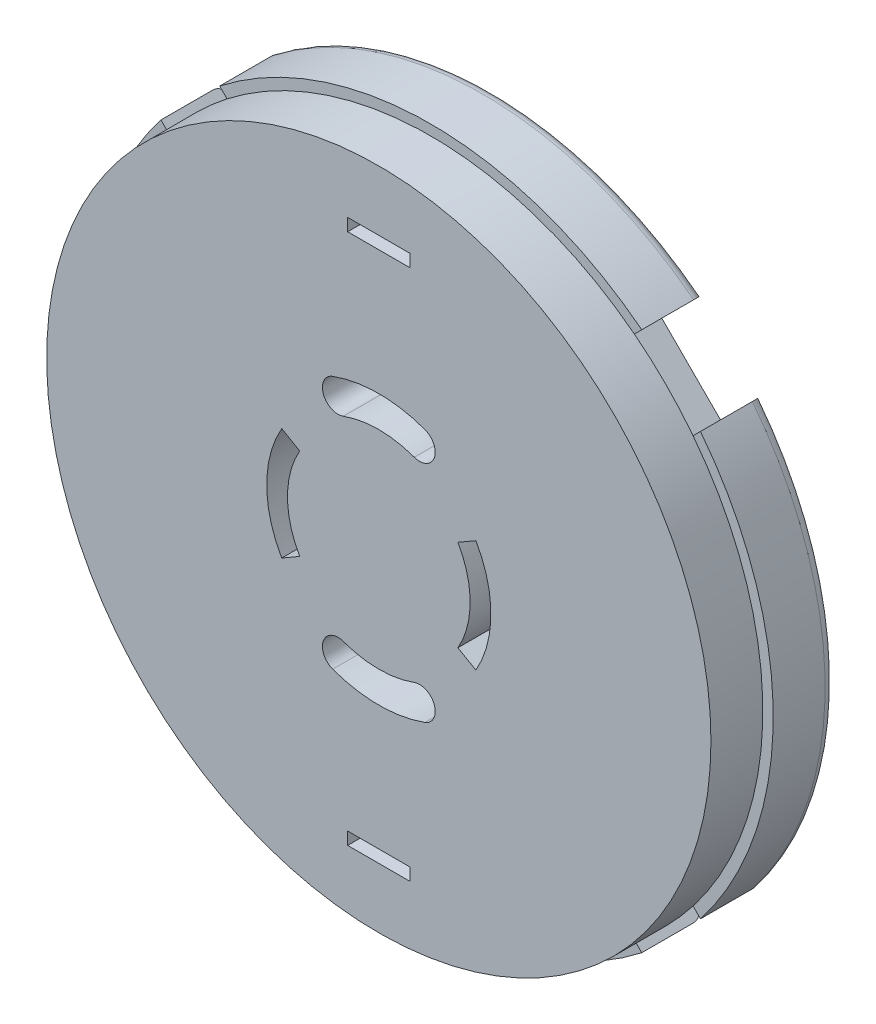
SolidWorks part; units mm, degrees
material "ABS"
ref_plane "Front Plane" through (0, 0, 0) normal (0, 0, 1) x (1, 0, 0)
ref_plane "Top Plane" through (0, 0, 0) normal (0, 1, 0) x (1, 0, 0)
ref_plane "Right Plane" through (0, 0, 0) normal (1, 0, 0) x (0, 0, -1)
sketch "Sketch1" plane through (0, 0, 0) normal (0, 0, 1) x (1, 0, 0)
  circle A0 centre (0, 0) radius 16.5
  dimension "D1" = 33
extrude "Boss-Extrude1" add sketch "Sketch1" against normal blind 3
sketch "Sketch2" plane through (0, 0, -3) normal (0, 0, -1) x (-1, 0, 0)
  circle A0 centre (0, 0) radius 4.5
  dimension "D1" = 9
extrude "Boss-Extrude2" add sketch "Sketch2" along normal blind 2
sketch "Sketch3" plane through (0, 0, -3) normal (0, 0, -1) x (-1, 0, 0)
  line L0 (10.253, 13.0815) -> (8.1317, 10.9602)
  line L5 (8.1317, 10.9602) -> (10.9602, 8.1317)
  line L6 (10.9602, 8.1317) -> (13.0815, 10.253)
  line L7 (13.0815, 10.253) -> (10.253, 13.0815)
  line L8 (0, 0) -> (9.5459, 9.5459) construction
  line L9 (0, 0) -> (0, 16.5) construction
  circle A0 centre (0, 0) radius 16.5 construction
  dimension "D2" = 4
  dimension "D1" = 45
  dimension "D3" = 3
extrude "Cut-Extrude1" cut sketch "Sketch3" against normal through all
pattern_circular "CirPattern1" count 4 over 360 about axis through (0, 0, -3) along (0, 0, 1) of "Cut-Extrude1" reverse direction yes
sketch "Sketch4" plane through (0, 0, 0) normal (0, 0, 1) x (1, 0, 0)
  circle A0 centre (0, 0) radius 16
  dimension "D1" = 32
extrude "Boss-Extrude3" add sketch "Sketch4" along normal blind 2.5
sketch "Sketch6" plane through (0, 0, -3) normal (0, 0, -1) x (-1, 0, 0)
  line L0 (-4.6765, 2.7) -> (-3.8105, 2.2)
  line L1 (-4.6765, -2.7) -> (-3.8105, -2.2)
  line L2 (0, 0) -> (-4.4, 0) construction
  line L3 (-4.6765, 2.7) -> (-4.6765, -2.7) construction
  arc A0 (-4.6765, 2.7) -> (-4.6765, -2.7) centre (0, 0) ccw
  arc A1 (-3.8105, 2.2) -> (-3.8105, -2.2) centre (0, 0) ccw
  dimension "D1" = 1
  dimension "D2" = 4.4
  dimension "D3" = 60
  dimension "D4" = 5.4
extrude "Cut-Extrude2" cut sketch "Sketch6" against normal through all
pattern_circular "CirPattern2" count 2 over 360 about axis through (0, 0, -3) along (0, 0, 1) of "Cut-Extrude2" reverse direction yes
sketch "Sketch7" plane through (0, 0, -3) normal (0, 0, -1) x (-1, 0, 0)
  line L0 (0, 0) -> (0, 5.75) construction
  line L1 (0, 0) -> (-1.9666, 5.4032) construction
  line L2 (0, 0) -> (1.9666, 5.4032) construction
  line L3 (-1.9666, 5.4032) -> (1.9666, 5.4032) construction
  arc A0 (-1.9666, 5.4032) -> (1.9666, 5.4032) centre (0, 0) cw construction
  arc A1 (2.2231, 6.108) -> (-2.2231, 6.108) centre (0, 0) ccw
  arc A2 (1.7101, 4.6985) -> (-1.7101, 4.6985) centre (0, 0) ccw
  arc A3 (1.7101, 4.6985) -> (2.2231, 6.108) centre (1.9666, 5.4032) ccw
  arc A4 (-2.2231, 6.108) -> (-1.7101, 4.6985) centre (-1.9666, 5.4032) ccw
  point P4 (0, 5.75)
  dimension "D1" = 0.75
  dimension "D2" = 5
  dimension "D3" = 40
  dimension "D4" = 3.9332
extrude "Cut-Extrude3" cut sketch "Sketch7" against normal through all
pattern_circular "CirPattern3" count 2 over 360 about axis through (0, 0, -3) along (0, 0, 1) of "Cut-Extrude3" reverse direction yes
sketch "Sketch8" plane through (0, 0, -3) normal (0, 0, -1) x (-1, 0, 0)
  line L0 (8.4853, -3.5355) -> (3.5355, -8.4853)
  line L1 (3.5355, -8.4853) -> (5.6569, -10.6066)
  line L2 (5.6569, -10.6066) -> (10.6066, -5.6569)
  line L3 (10.6066, -5.6569) -> (8.4853, -3.5355)
  line L4 (0, 0) -> (6.0104, -6.0104) construction
  line L5 (0, 0) -> (0, -16.5) construction
  line L6 (0, 0) -> (-7.0711, 7.0711) construction
  arc A0 (-10.167, -12.9954) -> (10.167, -12.9954) centre (0, 0) ccw construction
  circle A1 centre (-7.0711, 7.0711) radius 1.45
  dimension "D5" = 2.9
  dimension "D1" = 45
  dimension "D2" = 7
  dimension "D3" = 3
  dimension "D4" = 8.5
  dimension "D6" = 10
extrude "Cut-Extrude4" cut sketch "Sketch8" against normal blind 0.5
sketch "Sketch9" plane through (0, 0, -2.5) normal (0, 0, -1) x (-1, 0, 0)
  line L0 (-7.0711, 5.6211) -> (-7.0711, 8.5211)
  circle A0 centre (-7.0711, 7.0711) radius 1.45 construction
  circle A1 centre (-7.0711, 7.0711) radius 1.45 construction
extrude "Extrude-Thin1" add sketch "Sketch9" along normal up to surface (0.5 mm away) thin up to face at (-7.0711, -7.0711, -3) thin type two direction wall 0.25 second wall 0.25
sketch "Sketch10" plane through (0, 0, -2.5) normal (0, 0, -1) x (-1, 0, 0)
  line L0 (-8.5211, 7.0711) -> (-5.6211, 7.0711)
  arc A0 (-7.3211, 8.4994) -> (-7.3211, 5.6428) centre (-7.0711, 7.0711) ccw construction
  arc A1 (-6.8211, 5.6428) -> (-6.8211, 8.4994) centre (-7.0711, 7.0711) ccw construction
extrude "Extrude-Thin2" add sketch "Sketch10" along normal up to surface (0.5 mm away) thin up to face at (6.2211, 7.0711, -3) thin type two direction wall 0.25 second wall 0.25
sketch "Sketch11" plane through (0, 0, -3) normal (0, 0, -1) x (-1, 0, 0)
  line L0 (0, 0) -> (0, 12.8) construction
  line L1 (-1.5, 13.1) -> (1.5, 13.1)
  line L2 (-1.5, 13.1) -> (-1.5, 12.5)
  line L3 (-1.5, 12.5) -> (1.5, 12.5)
  line L4 (1.5, 13.1) -> (1.5, 12.5)
  line L5 (-1.5, 13.1) -> (1.5, 12.5) construction
  line L6 (-1.5, 12.5) -> (1.5, 13.1) construction
  point P0 (0, 12.8)
  dimension "D1" = 3
  dimension "D2" = 0.6
  dimension "D3" = 12.5
extrude "Cut-Extrude5" cut sketch "Sketch11" against normal through all
pattern_circular "CirPattern4" count 2 over 360 about axis through (0, 0, -3) along (0, 0, 1) of "Cut-Extrude5" reverse direction yes
fillet "Fillet1" radius 0.1 3 edges at (-4.5, 0, -5) (0, -4.5, -3) (0, 4.5, -3)
fillet "Fillet2" radius 0.5 4 edges at (16.5, 0, -3) (0, -16.5, -3) (-16.5, 0, -3) (0, 16.5, -3)
sketch "Эскиз1" plane through (0, 0, -5) normal (0, 0, -1) x (-1, 0, 0)
  circle A0 centre (0, 0) radius 1.5
  dimension "D1" = 3
extrude "Бобышка-Вытянуть1" add sketch "Эскиз1" along normal blind 2
